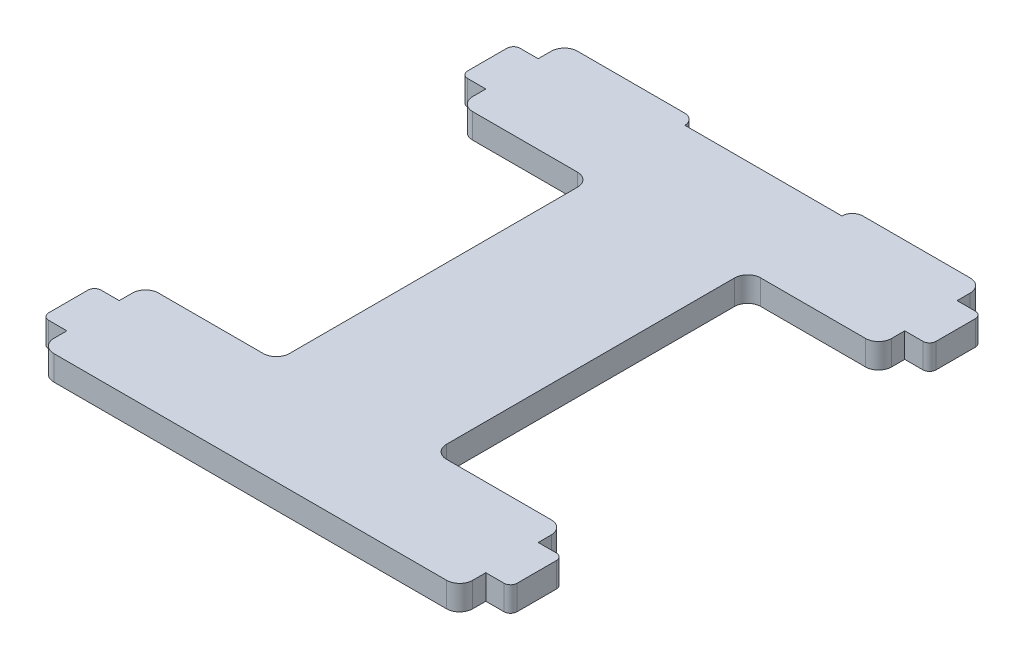
SolidWorks part; units mm, degrees
ref_plane "Front Plane" through (0, 0, 0) normal (0, 0, 1) x (1, 0, 0)
ref_plane "Top Plane" through (0, 0, 0) normal (0, 1, 0) x (1, 0, 0)
ref_plane "Right Plane" through (0, 0, 0) normal (1, 0, 0) x (0, 0, -1)
sketch "Sketch1" plane through (0, 0, 0) normal (0, 1, 0) x (1, 0, 0)
  line L0 (25.4, 19.05) -> (9.525, 19.05)
  line L1 (-25.4, -31.75) -> (25.4, -31.75)
  line L2 (-25.4, -31.75) -> (-25.4, -19.05)
  line L3 (-25.4, 31.75) -> (-9.525, 31.75)
  line L4 (25.4, -31.75) -> (25.4, -19.05)
  line L5 (-25.4, -31.75) -> (25.4, 31.75) construction
  line L6 (-25.4, 31.75) -> (25.4, -31.75) construction
  line L7 (9.525, 19.05) -> (9.525, -19.05)
  line L8 (9.525, -19.05) -> (25.4, -19.05)
  line L9 (-25.4, -19.05) -> (-9.525, -19.05)
  line L10 (-9.525, -19.05) -> (-9.525, 19.05)
  line L11 (-9.525, 19.05) -> (-25.4, 19.05)
  line L12 (0, -31.75) -> (0, 31.75) construction
  line L13 (-25.4, -19.05) -> (-25.4, 19.05) construction
  line L14 (-25.4, 19.05) -> (-25.4, 31.75)
  line L15 (25.4, -19.05) -> (25.4, 19.05) construction
  line L16 (25.4, 19.05) -> (25.4, 31.75)
  line L17 (-9.525, 31.75) -> (-9.525, 30.48)
  line L18 (-9.525, 30.48) -> (9.525, 30.48)
  line L19 (9.525, 30.48) -> (9.525, 31.75)
  line L20 (-9.525, 31.75) -> (0, 31.75) construction
  line L21 (9.525, 31.75) -> (25.4, 31.75)
  line L22 (0, 31.75) -> (9.525, 31.75) construction
  point P0 (0, 0)
  dimension "D1" = 50.8
  dimension "D2" = 63.5
  dimension "D3" = 12.7
  dimension "D4" = 12.7
  dimension "D5" = 19.05
  dimension "D6" = 19.05
  dimension "D7" = 1.27
extrude "Boss-Extrude1" add sketch "Sketch1" along normal mid plane 3
fillet "Fillet1" radius 1.5875 12 edges at (25.4, 0, -19.05) (9.525, 0, -19.05) (9.525, 0, 19.05) (25.4, 0, 19.05) (25.4, 0, 31.75) (-25.4, 0, 19.05) (-9.525, 0, 19.05) (-9.525, 0, -19.05) (-25.4, 0, -19.05) (-25.4, 0, -31.75) (-25.4, 0, 31.75) (25.4, 0, -31.75)
sketch "Sketch2" plane through (0, 1.5, 0) normal (0, 1, 0) x (1, 0, 0)
  line L5 (-25.4, 19.05) -> (-25.4, 31.75) construction
  line L6 (-26.9, 25.4) -> (-25.4, 25.4) construction
  line L12 (-25.4, -31.75) -> (-25.4, -19.05) construction
  line L13 (25.4, 19.05) -> (25.4, 31.75) construction
  line L14 (25.4, -31.75) -> (25.4, -19.05) construction
  line L15 (-26.9, -25.4) -> (-25.4, -25.4) construction
  line B0 (-28.4, 22.225) -> (-25.4, 22.225)
  line B1 (-28.4, 22.225) -> (-28.4, 28.575)
  line B2 (-28.4, 28.575) -> (-25.4, 28.575)
  line B3 (-25.4, 22.225) -> (-25.4, 28.575)
  line B4 (-28.4, 22.225) -> (-25.4, 28.575) construction
  line B5 (-28.4, 28.575) -> (-25.4, 22.225) construction
  line B6 (25.4, 22.225) -> (28.4, 22.225)
  line B7 (25.4, 22.225) -> (25.4, 28.575)
  line B8 (25.4, 28.575) -> (28.4, 28.575)
  line B9 (28.4, 22.225) -> (28.4, 28.575)
  line B10 (25.4, -28.575) -> (28.4, -28.575)
  line B11 (25.4, -28.575) -> (25.4, -22.225)
  line B12 (25.4, -22.225) -> (28.4, -22.225)
  line B13 (28.4, -28.575) -> (28.4, -22.225)
  line B14 (-28.4, -28.575) -> (-25.4, -28.575)
  line B15 (-28.4, -28.575) -> (-28.4, -22.225)
  line B16 (-28.4, -22.225) -> (-25.4, -22.225)
  line B17 (-25.4, -28.575) -> (-25.4, -22.225)
sketch_block_instance "Block1-1"
sketch_block "Block1" parameters "D1"=6.35, "D2"=3
sketch_block_instance "Block1-2"
sketch_block_instance "Block1-3"
sketch_block_instance "Block1-4"
extrude "Boss-Extrude2" add sketch "Sketch2" against normal up to surface (3 mm away) up to face at (0, -1.5, -4.445)
fillet "Fillet2" radius 0.7937 8 edges at (-28.4, 0, 28.575) (-28.4, 0, 22.225) (28.4, 0, 22.225) (28.4, 0, 28.575) (28.4, 0, -28.575) (28.4, 0, -22.225) (-28.4, 0, -28.575) (-28.4, 0, -22.225)
fillet "Fillet3" radius 1.27 2 edges at (9.525, 0, -31.75) (-9.525, 0, -31.75)
